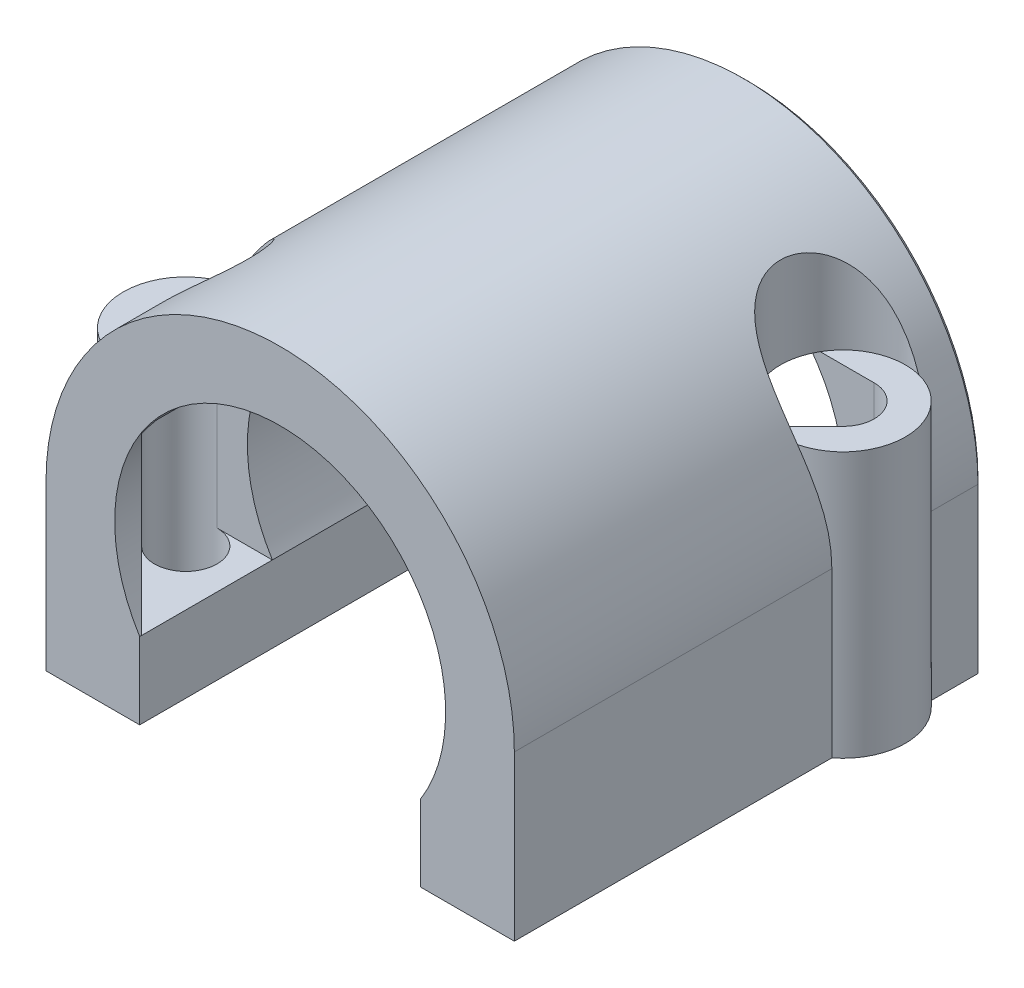
SolidWorks part; units mm, degrees
material "Custom Plastic"
ref_plane "Front Plane" through (0, 0, 0) normal (0, 0, 1) x (1, 0, 0)
ref_plane "Top Plane" through (0, 0, 0) normal (0, 1, 0) x (1, 0, 0)
ref_plane "Right Plane" through (0, 0, 0) normal (1, 0, 0) x (0, 0, -1)
sketch "Sketch1" plane through (0, 0, 0) normal (0, 0, 1) x (1, 0, 0)
  line L0 (-9, -10.5) -> (9, -10.5)
  line L1 (-9, -10.5) -> (-15, -10.5)
  line L2 (-15, -10.5) -> (15, -10.5) construction
  line L3 (-9, -5.4083) -> (-9, -10.5) construction
  line L4 (-15, 0) -> (-15, -10.5)
  line L5 (9, -5.4083) -> (9, -10.5) construction
  line L6 (9, -10.5) -> (15, -10.5)
  line L7 (15, -10.5) -> (15, 0)
  arc A1 (15, 0) -> (-15, 0) centre (0, 0) ccw
  circle A2 centre (0, 0) radius 10.5 construction
  dimension "D1" = 21
  dimension "D2" = 4.5
  dimension "D3" = 18
extrude "Boss-Extrude1" add sketch "Sketch1" along normal blind 30
sketch "Sketch4" plane through (0, -10.5, 0) normal (0, -1, 0) x (1, 0, 0)
  line L0 (0, 0) -> (0, 30) construction
  line L1 (-15, 30) -> (15, 30) construction
  line L2 (11, 29) -> (11, -1) construction
  line L4 (12.55, 6.5) -> (-12.55, 23.5) construction
  line L5 (-12.55, 27.5) -> (-12.55, 19.5)
  line L6 (12.55, 2.5) -> (12.55, 10.5)
  circle A0 centre (0, 15) radius 11 construction
  circle A1 centre (12.55, 6.5) radius 1.55 construction
  arc A2 (12.55, 2.5) -> (12.55, 10.5) centre (12.55, 6.5) ccw
  arc A3 (-12.55, 27.5) -> (-12.55, 19.5) centre (-12.55, 23.5) ccw
  dimension "D1" = 22
  dimension "D2" = 3.1
  dimension "D3" = 8
  dimension "D4" = 17
extrude "Boss-Extrude2" add sketch "Sketch4" against normal blind 17
sketch "Sketch2" plane through (0, -10.5, 0) normal (0, -1, 0) x (1, 0, 0)
  line L0 (11, 29) -> (11, -1) construction
  line L1 (0, 0) -> (0, 30) construction
  line L4 (12.55, 6.5) -> (-12.55, 23.5) construction
  circle A0 centre (12.55, 6.5) radius 1.55 construction
  arc A1 (-13.5185, 27.381) -> (-13.5185, 19.619) centre (-12.55, 23.5) ccw construction
  circle A2 centre (-12.55, 23.5) radius 1.55 construction
  circle A3 centre (12.55, 6.5) radius 2
  circle A4 centre (-12.55, 23.5) radius 2
  arc A6 (13.5185, 2.619) -> (13.5185, 10.381) centre (12.55, 6.5) ccw construction
  dimension "D1" = 3.1
  dimension "D4" = 4
extrude "Cut-Extrude7" cut sketch "Sketch2" against normal through all
sketch "Sketch3" plane through (0, -10.5, 0) normal (0, -1, 0) x (1, 0, 0)
  circle A0 centre (12.55, 6.5) radius 4
  arc A1 (12.55, 2.5) -> (12.55, 10.5) centre (12.55, 6.5) ccw construction
  arc A2 (-12.55, 27.5) -> (-12.55, 19.5) centre (-12.55, 23.5) ccw construction
  circle A3 centre (-12.55, 23.5) radius 4
  dimension "D1" = 8
extrude "Cut-Extrude2" cut sketch "Sketch3" against normal through all from offset 17 offset against normal yes
sketch "Sketch5" plane through (0, 0, 30) normal (0, 0, 1) x (1, 0, 0)
  line L1 (0, 0) -> (0, -10.5) construction
  line L2 (-11, -10.5) -> (11, -10.5) construction
  line L3 (-9, -10.5) -> (9, -10.5)
  line L4 (9, -10.5) -> (9, -5.6)
  line L5 (-9, -10.5) -> (-9, -5.6)
  arc A0 (9, -5.6) -> (-9, -5.6) centre (0, 0) ccw
  dimension "D1" = 10.6
  dimension "D2" = 18
extrude "Cut-Extrude3" cut sketch "Sketch5" against normal through all
sketch "Sketch6" plane through (0, 0, 0) normal (0, 1, 0) x (1, 0, 0)
  line L0 (0, 0) -> (0, -30) construction
  line L1 (0, -24.9142) -> (-13.9642, -24.9142) construction
  line L2 (0, -24.9142) -> (0, -21.5)
  line L3 (0, -21.5) -> (-12.55, -21.5)
  line L4 (-13.9642, -24.9142) -> (-12.55, -21.5)
  line L7 (0, -7.9142) -> (13.9642, -7.9142) construction
  line L8 (0, -7.9142) -> (0, -4.5)
  line L9 (0, -4.5) -> (12.55, -4.5)
  line L10 (13.9642, -7.9142) -> (12.55, -4.5)
  line L11 (0, -7.9142) -> (12.55, -4.5) construction
  line L12 (0, -4.5) -> (13.9642, -7.9142) construction
  line L30 (13.9642, -7.9142) -> (9, -12.8784)
  line L32 (9, -12.8784) -> (0, -7.9142)
  line L33 (-13.9642, -24.9142) -> (-9, -29.8784)
  line L35 (-9, -29.8784) -> (0, -24.9142)
  line L36 (-9, 0) -> (-9, -30) construction
  line L37 (9, 0) -> (9, -30) construction
  line L38 (12.55, -2.5) -> (12.55, -10.5) construction
  circle A2 centre (-12.55, -23.5) radius 2 construction
  circle A3 centre (12.55, -6.5) radius 2 construction
  point P0 (-6.275, -23.5)
  point P8 (6.9821, -6.5)
  dimension "D1" = 45
  dimension "D2" = 45
extrude "Cut-Extrude8" cut sketch "Sketch6" against normal up to vertex (5.6 mm away) and the other way up to vertex (6.5 mm away) up to point (-9, -5.6, 30) other way up to point (-13.5185, 6.5, 19.619)
chamfer "Chamfer1" distance 0.3 angle 45 8 edges at (15, -5.25, 0) (0, 15, 0) (-15, -5.25, 0) (-12, -10.5, 0) (-9, -8.05, 0) (0, 10.6, 0) (9, -8.05, 0) (12, -10.5, 0)
